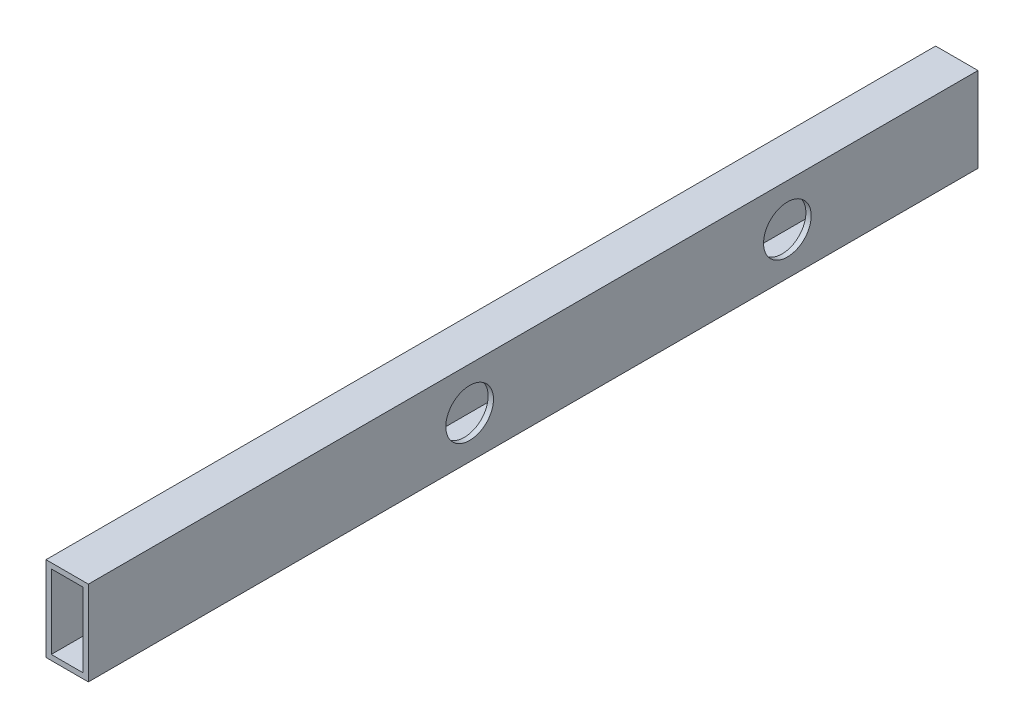
SolidWorks part; units mm, degrees
material "1060 Alloy"
ref_plane "Front Plane" through (0, 0, 0) normal (0, 0, 1) x (1, 0, 0)
ref_plane "Top Plane" through (0, 0, 0) normal (0, 1, 0) x (1, 0, 0)
ref_plane "Right Plane" through (0, 0, 0) normal (1, 0, 0) x (0, 0, -1)
sketch "Sketch1" plane through (0, 0, 0) normal (0, 0, 1) x (1, 0, 0)
  line L1 (-12.7, -25.4) -> (12.7, -25.4)
  line L2 (-12.7, -25.4) -> (-12.7, 25.4)
  line L3 (-12.7, 25.4) -> (12.7, 25.4)
  line L4 (12.7, -25.4) -> (12.7, 25.4)
  line L5 (-12.7, -25.4) -> (12.7, 25.4) construction
  line L6 (-12.7, 25.4) -> (12.7, -25.4) construction
  point P0 (0, 0)
  dimension "D1" = 25.4
  dimension "D2" = 50.8
extrude "Extrude-Thin1" add sketch "Sketch1" along normal blind 533.4 thin thin type one direction reverse wall 3.175
sketch "Sketch2" plane through (12.7, 0, 0) normal (1, 0, 0) x (0, 0, -1)
  line L0 (0, -25.4) -> (0, 25.4) construction
  line L1 (-533.4, -25.4) -> (-533.4, 25.4) construction
  circle A0 centre (-304.8, 0) radius 14.2875
  circle A1 centre (-114.3, 0) radius 14.2875
  dimension "D1" = 28.575
  dimension "D2" = 114.3
  dimension "D3" = 228.6
extrude "Cut-Extrude1" cut sketch "Sketch2" against normal through all
